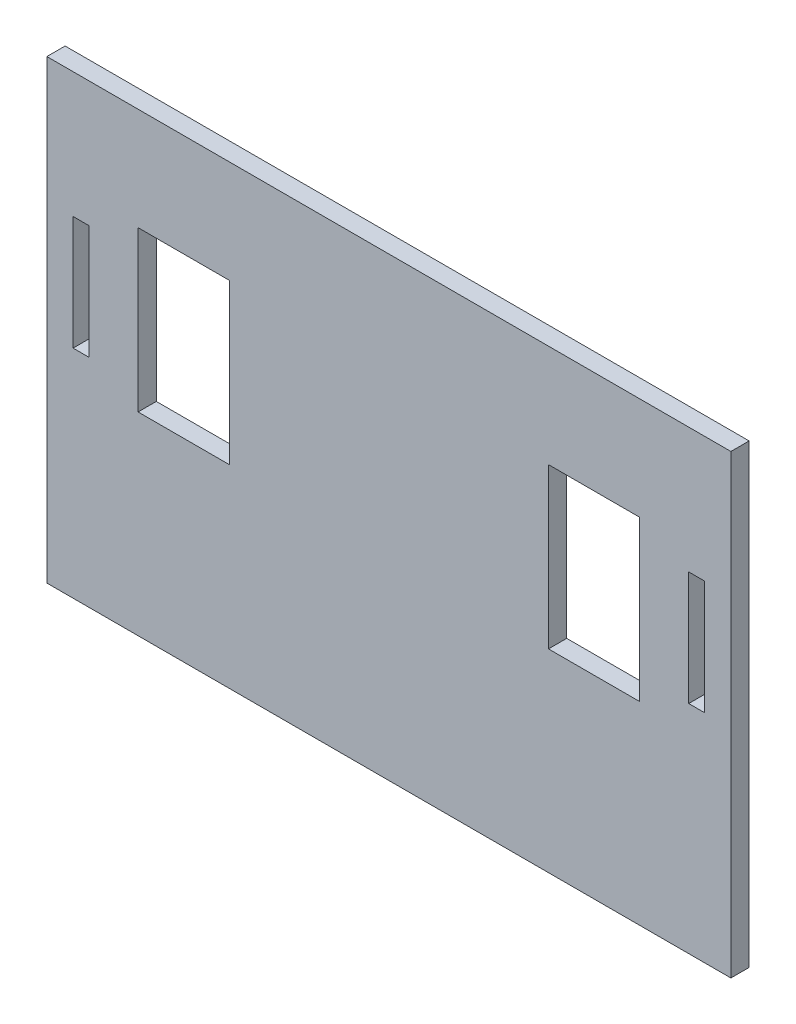
SolidWorks part; units mm, degrees
ref_plane "Front" through (0, 0, 0) normal (0, 0, 1) x (1, 0, 0)
ref_plane "Top" through (0, 0, 0) normal (0, 1, 0) x (1, 0, 0)
ref_plane "Right" through (0, 0, 0) normal (1, 0, 0) x (0, 0, -1)
sketch "Esquisse1" plane through (0, 0, 0) normal (0, 0, 1) x (1, 0, 0)
  line L1 (0, 0) -> (300, 0)
  line L2 (0, 0) -> (0, 200)
  line L3 (0, 200) -> (300, 200)
  line L4 (300, 0) -> (300, 200)
  dimension "D1" = 300
  dimension "D2" = 200
extrude "Boss.-Extru.1" add sketch "Esquisse1" along normal blind 8
sketch "Esquisse2" plane through (0, 0, 8) normal (0, 0, 1) x (1, 0, 0)
  line L0 (150, 200) -> (150, 0) construction
  line L1 (40, 85) -> (80, 85)
  line L2 (40, 85) -> (40, 155)
  line L3 (40, 155) -> (80, 155)
  line L4 (80, 85) -> (80, 155)
  line L5 (300, 200) -> (0, 200) construction
  line L6 (0, 0) -> (300, 0) construction
  line L7 (80, 120) -> (150, 120) construction
  line L8 (60, 85) -> (60, 155) construction
  line L9 (40, 120) -> (18.5, 120) construction
  line L10 (15, 95) -> (15, 145) construction
  line L11 (11.5, 95) -> (18.5, 95)
  line L12 (11.5, 95) -> (11.5, 145)
  line L13 (11.5, 145) -> (18.5, 145)
  line L14 (18.5, 95) -> (18.5, 145)
  line L15 (285, 95) -> (285, 145) construction
  line L16 (260, 120) -> (281.5, 120) construction
  line L17 (240, 85) -> (240, 155) construction
  line L18 (281.5, 95) -> (281.5, 145)
  line L19 (288.5, 145) -> (281.5, 145)
  line L20 (288.5, 95) -> (288.5, 145)
  line L21 (288.5, 95) -> (281.5, 95)
  line L22 (220, 85) -> (220, 155)
  line L23 (260, 155) -> (220, 155)
  line L24 (260, 85) -> (260, 155)
  line L25 (260, 85) -> (220, 85)
  dimension "D1" = 80
  dimension "D2" = 70
  dimension "D3" = 40
  dimension "D4" = 180
  dimension "D5" = 7
  dimension "D6" = 50
  dimension "D7" = 270
extrude "Enlèv. mat.-Extru.1" cut sketch "Esquisse2" against normal through all
